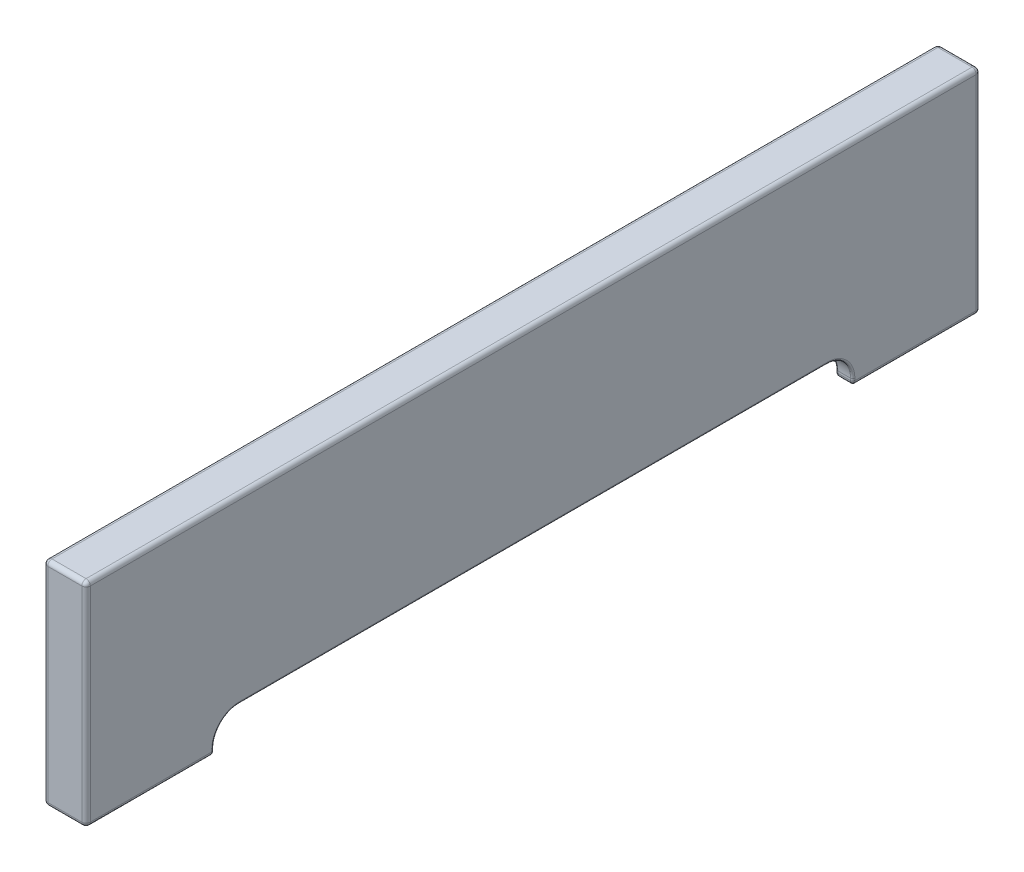
SolidWorks part; units mm, degrees
ref_plane "Front Plane" through (0, 0, 0) normal (0, 0, 1) x (1, 0, 0)
ref_plane "Top Plane" through (0, 0, 0) normal (0, 1, 0) x (1, 0, 0)
ref_plane "Right Plane" through (0, 0, 0) normal (1, 0, 0) x (0, 0, -1)
sketch "Sketch1" plane through (0, 0, 0) normal (1, 0, 0) x (0, 0, -1)
  line L1 (210, -50) -> (-210, -50)
  line L2 (210, -50) -> (210, 50)
  line L3 (210, 50) -> (-210, 50)
  line L4 (-210, -50) -> (-210, 50)
  line L5 (210, -50) -> (-210, 50) construction
  line L6 (210, 50) -> (-210, -50) construction
  point P0 (0, 0)
  dimension "D1" = 420
  dimension "D2" = 100
extrude "Boss-Extrude1" add sketch "Sketch1" against normal blind 20
sketch "Sketch3" plane through (0, 0, 0) normal (1, 0, 0) x (0, 0, -1)
  line L0 (-210, -50) -> (210, -50) construction
  line L1 (-150, -50) -> (150, -50)
  line L2 (-150, -50) -> (-150, -47)
  line L3 (-138, -35) -> (138, -35)
  line L4 (150, -50) -> (150, -47)
  arc A0 (138, -35) -> (150, -47) centre (138, -47) cw
  arc A1 (-150, -47) -> (-138, -35) centre (-138, -47) cw
  point P4 (0, -50)
  point P10 (150, -35)
  point P13 (-150, -35)
  dimension "D3" = 12
  dimension "D1" = 15
  dimension "D2" = 300
extrude "Cut-Extrude2" cut sketch "Sketch3" against normal blind 15
sketch "Sketch4" plane through (-15, 0, 0) normal (1, 0, 0) x (0, 0, -1)
  line L0 (-150, -50) -> (150, -50) construction
  line L1 (-155, -50) -> (155, -50)
  line L2 (-155, -50) -> (-155, -47)
  line L3 (-140, -32) -> (140, -32)
  line L4 (155, -50) -> (155, -47)
  arc A0 (140, -32) -> (155, -47) centre (140, -47) cw
  arc A1 (-155, -47) -> (-140, -32) centre (-140, -47) cw
  point P6 (0, -32)
  point P10 (155, -32)
  point P13 (-155, -32)
  dimension "D3" = 15
  dimension "D1" = 310
  dimension "D2" = 18
extrude "Cut-Extrude3" cut sketch "Sketch4" along normal blind 7
fillet "Fillet1" radius 1 20 edges at (-8, -48.5, -155) (-8, -36.3934, -150.6066) (-8, -32, 0) (-8, -48.5, 155) (0, -48.5, -150) (0, -38.5147, -146.4853) (0, -48.5, 150) (0, -38.5147, 146.4853) (-8, -48.5, -150) (-8, -38.5147, -146.4853) (-8, -48.5, 150) (-8, -38.5147, 146.4853) (-15, -48.5, -155) (-15, -36.3934, -150.6066) (-15, -48.5, 155) (-15, -36.3934, 150.6066) (-8, -36.3934, 150.6066) (0, -35, 0) (-8, -35, 0) (-15, -32, 0)
fillet "Fillet2" radius 2 28 edges at (-10, -50, -210) (-0.2929, -50, 150.2929) (-4, -50, 150) (-7.7071, -50, 150.2929) (-8, -50, 152.5) (-8.2929, -50, 154.7071) (-11.5, -50, 155) (-14.7071, -50, 154.7071) (-15, -50, 0) (-14.7071, -50, -154.7071) (-11.5, -50, -155) (-8.2929, -50, -154.7071) (-8, -50, -152.5) (-7.7071, -50, -150.2929) (-4, -50, -150) (-0.2929, -50, -150.2929) (-10, -50, 210) (-20, -50, 0) (-20, 0, -210) (-20, 0, 210) (-10, 50, 210) (-20, 50, 0) (-10, 50, -210) (0, -50, 180.5) (0, 0, 210) (0, 50, 0) (0, 0, -210) (0, -50, -180.5)
